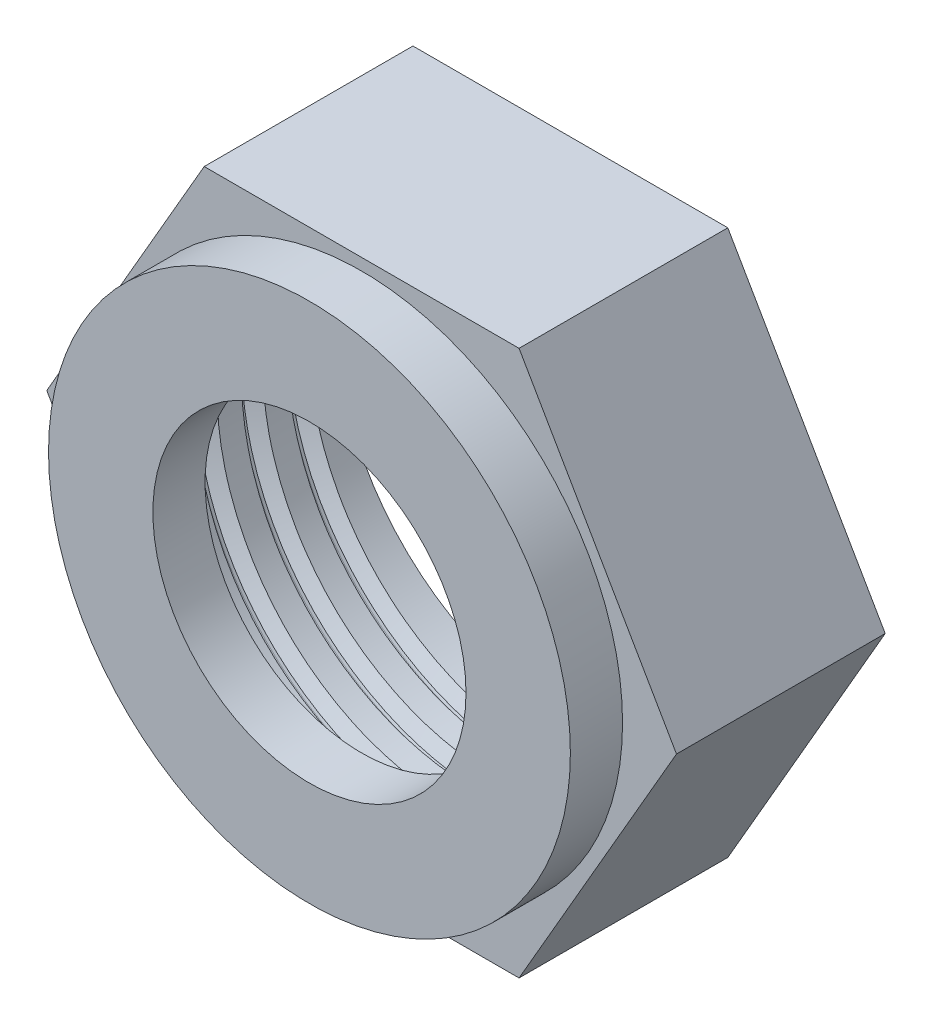
SolidWorks part; units mm, degrees
ref_plane "Front Plane" through (0, 0, 0) normal (0, 0, 1) x (1, 0, 0)
ref_plane "Top Plane" through (0, 0, 0) normal (0, 1, 0) x (1, 0, 0)
ref_plane "Right Plane" through (0, 0, 0) normal (1, 0, 0) x (0, 0, -1)
sketch "Sketch1" plane through (0, 0, 0) normal (0, 0, 1) x (1, 0, 0)
  line L0 (6.0333, 10.45) -> (-6.0333, -10.45) construction
  line L1 (6.0333, 10.45) -> (-6.0333, 10.45)
  line L2 (-6.0333, 10.45) -> (-12.0666, 0)
  line L3 (-12.0666, 0) -> (-6.0333, -10.45)
  line L4 (-6.0333, -10.45) -> (6.0333, -10.45)
  line L5 (6.0333, -10.45) -> (12.0666, 0)
  line L6 (12.0666, 0) -> (6.0333, 10.45)
  circle A0 centre (0, 0) radius 9
  circle A1 centre (0, 0) radius 10
  circle A2 centre (0, 0) radius 6
  dimension "D1" = 18
  dimension "D2" = 12
  dimension "D3" = 20
extrude "upp cap" add sketch "Sketch1" along normal blind 2 contours A2 | A1
extrude "Boss-Extrude2" add sketch "Sketch1<3>" against normal up to surface (8 mm away) contours L3 L4 L5 L6 L1 L2 | A0
sketch "Sketch1<3>" plane through (0, 0, 0) normal (0, 0, 1) x (1, 0, 0) same geometry as "Sketch1"
sketch "Sketch2" plane through (0, 0, 0) normal (0, 0, 1) x (1, 0, 0)
  circle A0 centre (0, 0) radius 9
  dimension "D1" = 18
curve "Helix/Spiral1" pitch 1.75 height 7.875 radius 9 centre (0, 0, 0) axis (0, 0, -1) start towards (0, 1, 0)
sketch "cut" plane through (0, 0, 0) normal (1, 0, 0) x (0, 0, -1)
  line L0 (0, 9) -> (0, 9.51) construction
  line L1 (0, 10.45) -> (0, 0) construction
  line L2 (0, 9) -> (0, -9) construction
  line L3 (0, 9.51) -> (-0.1127, 9.51)
  line L4 (-0.1127, 9.51) -> (-0.4072, 9)
  line L5 (-0.4072, 9) -> (0.4072, 9)
  line L6 (0.4072, 9) -> (0.1127, 9.51)
  line L7 (0.1127, 9.51) -> (0, 9.51)
  dimension "D1" = 0.51
  dimension "D2" = 60
  dimension "D3" = 0.1127
sweep "Cut-Sweep2" cut profiles "cut" path "Helix/Spiral1" align with end faces yes
